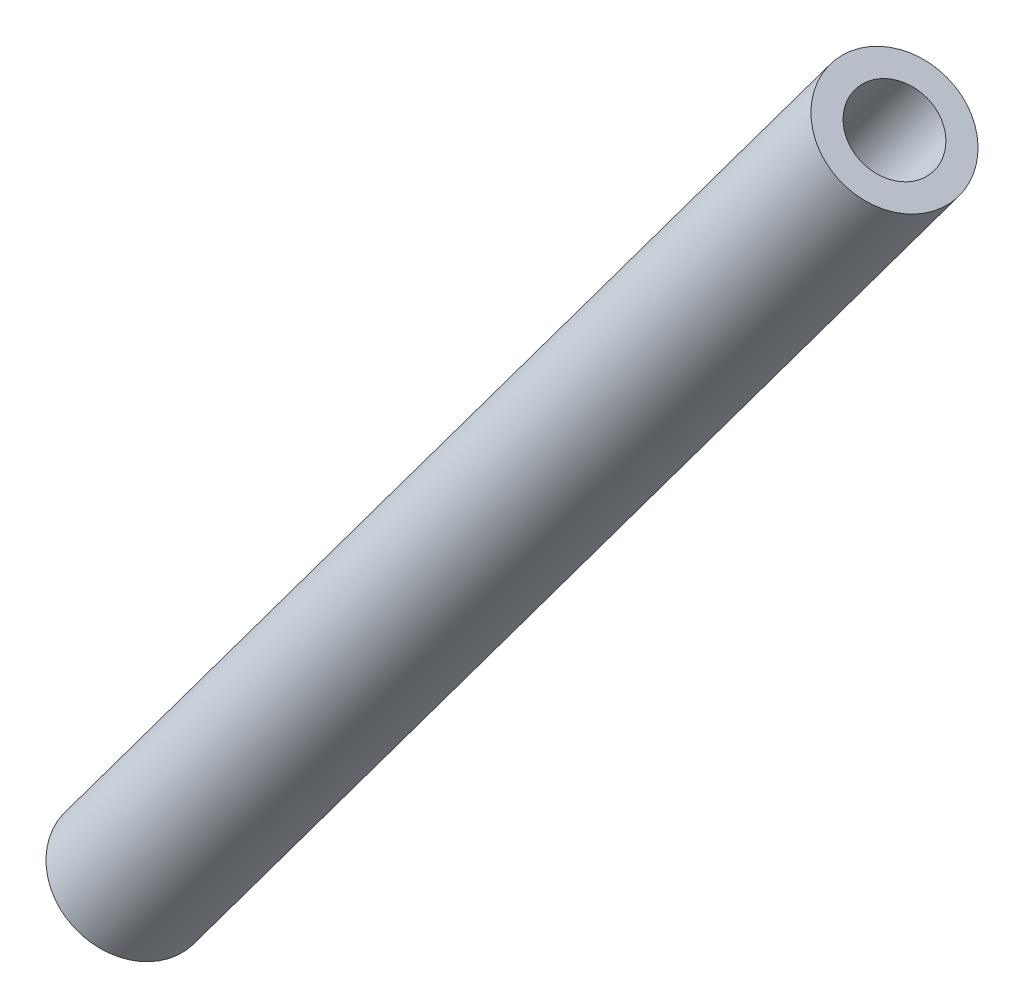
SolidWorks part; units mm, degrees
material "Silicon Rubber"
ref_plane "X-Y Datum" through (0, 0, 0) normal (0, 0, 1) x (1, 0, 0)
ref_plane "X-Z Datum" through (0, 0, 0) normal (0, 1, 0) x (1, 0, 0)
ref_plane "Y-Z Datum" through (0, 0, 0) normal (1, 0, 0) x (0, 0, -1)
sketch3d "3DSketch1"
  line L0 (0, 0, 0) -> (121.1605, 163.1268, 0)
  dimension "D1" = 203.2
sweep "Sweep1" add path "3DSketch1" circular profile diameter 20.6375 parameters "D3"=20.6375
sweep "Cut-Sweep1" cut path "3DSketch1<2>" circular profile diameter 12.7 parameters "D3"=12.7
sketch3d "3DSketch1<2>" same geometry as "3DSketch1"
sketch3d "3DSketch2"
  line L0 (0, 0, 0) -> (121.1605, 163.1268, 0) construction
  circle A1 centre (60.5803, 81.5634, 0) radius 6.35 construction
  circle A4 centre (121.1605, 163.1268, 0) radius 6.35 construction
  point P4 (56.794, 76.4657, 0)
  point P8 (117.3743, 158.0291, 0)
